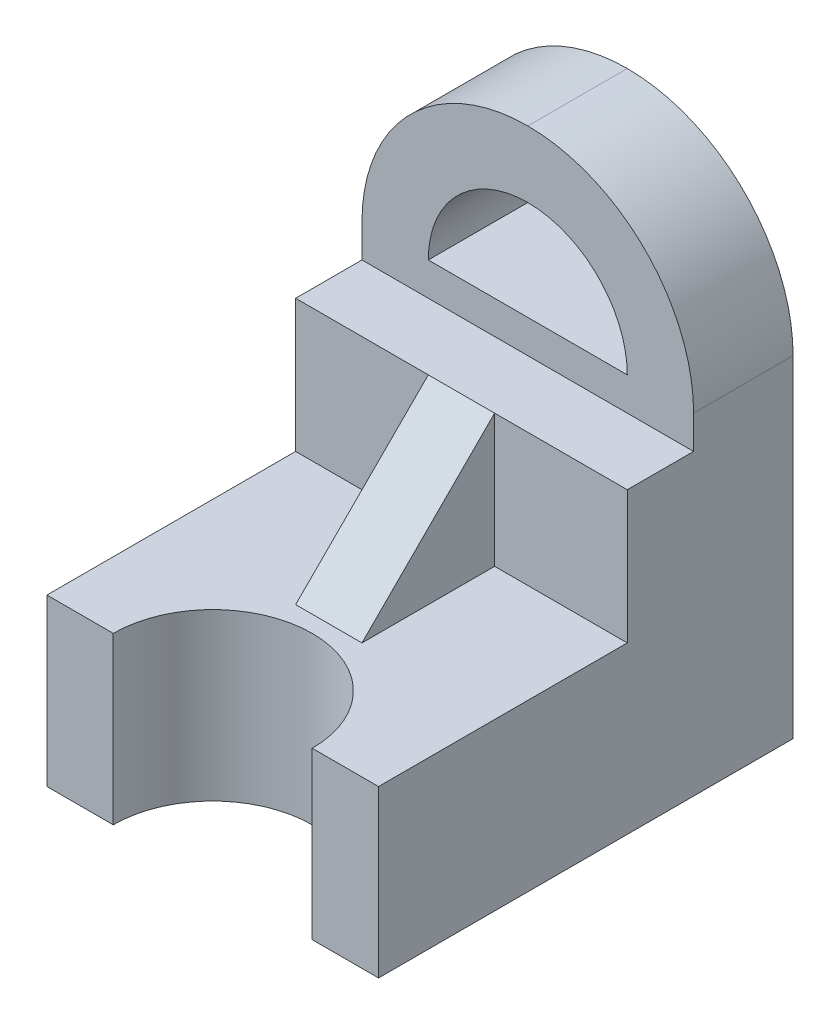
SolidWorks part; units mm, degrees
ref_plane "Front Plane" through (0, 0, 0) normal (0, 0, 1) x (1, 0, 0)
ref_plane "Top Plane" through (0, 0, 0) normal (0, 1, 0) x (1, 0, 0)
ref_plane "Right Plane" through (0, 0, 0) normal (1, 0, 0) x (0, 0, -1)
sketch "Sketch1" plane through (0, 0, 0) normal (0, 1, 0) x (1, 0, 0)
  line L0 (30, -62.5) -> (50, -62.5)
  line L1 (-50, 62.5) -> (50, 62.5)
  line L2 (-50, 62.5) -> (-50, -62.5)
  line L3 (-50, -62.5) -> (-30, -62.5)
  line L4 (50, 62.5) -> (50, -62.5)
  line L5 (-50, 62.5) -> (50, -62.5) construction
  line L6 (-50, -62.5) -> (50, 62.5) construction
  arc A0 (30, -62.5) -> (-30, -62.5) centre (0, -62.5) ccw
  point P1 (0, 0)
  dimension "D3" = 60
  dimension "D1" = 100
  dimension "D2" = 125
  dimension "D4" = 62.5
  dimension "D5" = 50
extrude "Boss-Extrude1" add sketch "Sketch1" along normal blind 50
sketch "Sketch2" plane through (0, 0, 0) normal (0, 1, 0) x (1, 0, 0)
  line L0 (50, -62.5) -> (50, 62.5) construction
  line L1 (-50, 62.5) -> (50, 62.5)
  line L2 (-50, 62.5) -> (-50, 12.5)
  line L3 (-50, 12.5) -> (50, 12.5)
  line L4 (50, 62.5) -> (50, 12.5)
  dimension "D1" = 50
extrude "Boss-Extrude2" add sketch "Sketch2" along normal blind 90
sketch "Sketch3" plane through (0, 0, 0) normal (0, 1, 0) x (1, 0, 0)
  line L0 (50, 12.5) -> (50, 62.5) construction
  line L1 (-50, 62.5) -> (50, 62.5)
  line L2 (-50, 62.5) -> (-50, 32.5)
  line L3 (-50, 32.5) -> (50, 32.5)
  line L4 (50, 62.5) -> (50, 32.5)
  dimension "D1" = 30
extrude "Boss-Extrude3" add sketch "Sketch3" along normal blind 150
sketch "Sketch4" plane through (0, 0, 0) normal (1, 0, 0) x (0, 0, -1)
  line L0 (12.5, 90) -> (-27.5, 50)
  line L1 (-62.5, 50) -> (12.5, 50) construction
  line L2 (-27.5, 50) -> (12.5, 50)
  line L3 (12.5, 50) -> (12.5, 90)
  dimension "D1" = 45
extrude "Boss-Extrude4" add sketch "Sketch4" along normal mid plane 20
fillet "Fillet1" radius 50 2 edges at (-50, 150, -47.5) (50, 150, -47.5)
sketch "Sketch6" plane through (0, 0, 0) normal (0, 0, 1) x (1, 0, 0)
  line L0 (-30, 100) -> (30, 100)
  line L1 (50, 90) -> (-50, 90) construction
  line L2 (-50, 100) -> (-50, 90) construction
  arc A0 (30, 100) -> (-30, 100) centre (0, 100) ccw
  point P5 (0, 100)
  dimension "D1" = 30
  dimension "D2" = 10
  dimension "D3" = 50
extrude "Cut-Extrude1" cut sketch "Sketch6" against normal through all
